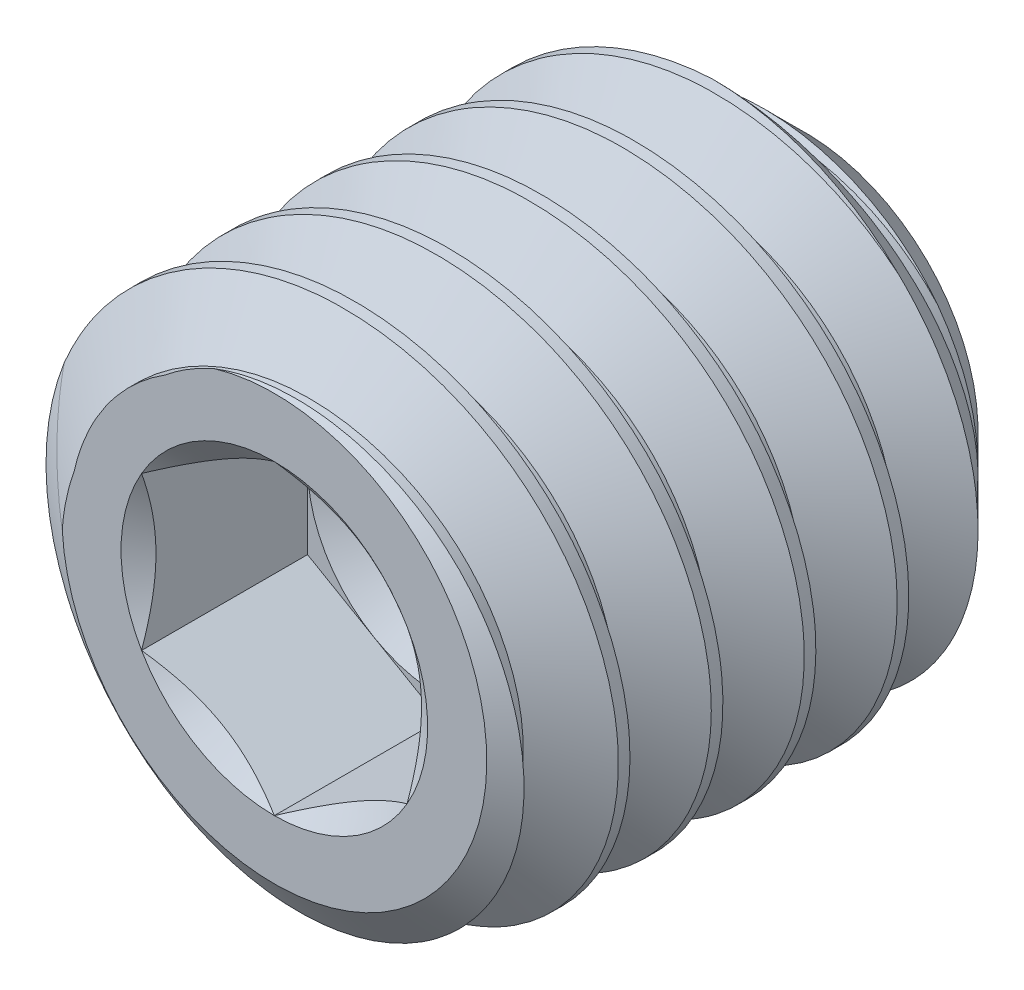
SolidWorks part; units mm, degrees
ref_plane "Front" through (0, 0, 0) normal (0, 0, 1) x (1, 0, 0)
ref_plane "Top" through (0, 0, 0) normal (0, 1, 0) x (1, 0, 0)
ref_plane "Right" through (0, 0, 0) normal (1, 0, 0) x (0, 0, -1)
sketch "Revolve Profile" plane through (0, 0, 0) normal (1, 0, 0) x (0, 0, -1)
  line L0 (-2, 0) -> (-2, 1.6)
  line L1 (-2, 1.6) -> (-1.7199, 2)
  line L2 (-1.7199, 2) -> (1.3, 2)
  line L3 (1.3, 2) -> (2, 1.3)
  line L4 (-0.21, 2) -> (-0.21, -2) construction
  line L5 (2, 0) -> (-2, 0)
  line L6 (-2, 1.6) -> (-2, -1.6) construction
  line L7 (2, 0) -> (2, 1.3)
  point P11 (-0.21, 0)
  dimension "Length" = 4
  dimension "D3" = 35
  dimension "D6" = 45
  dimension "Dia" = 4
  dimension "D1" = 3.2
  dimension "D2" = 0.7
revolve "Body Revolve" add sketch "Revolve Profile" angle 360 about L5
ref_plane "Plane1" through (0, 0, -2) normal (0, 0, 1) x (1, 0, 0)
sketch "Sketch27" plane through (0, 0, -2) normal (0, 0, 1) x (1, 0, 0)
  circle A0 centre (0, 0) radius 2 construction
  circle A1 centre (0, 0) radius 2
curve "Helix/Spiral" pitch 0.7 height 4.7 radius 2 centre (0, 0, -2) axis (0, 0, 1) start towards (0, 1, 0)
sketch "Sketch28" plane through (0, 0, 0) normal (1, 0, 0) x (0, 0, -1)
  line L0 (2, 2) -> (2.6125, 2)
  line L1 (2.6125, 2) -> (2.35, 1.5453)
  line L2 (2.35, 1.5453) -> (2.2625, 1.5453)
  line L3 (2.2625, 1.5453) -> (2, 2)
  line L4 (2.1313, 1.7727) -> (2.4813, 1.7727) construction
  line L6 (-1.7199, 2) -> (1.3, 2) construction
  dimension "D1" = 0.0875
  dimension "D3" = 60
  dimension "D2" = 0.35
sweep "Thread Sweep" cut profiles "Sketch28" path "Helix/Spiral" align with end faces yes
sketch "Hex Sketch" plane through (0, 0, 2) normal (0, 0, 1) x (1, 0, 0)
  line L1 (0, 1.1547) -> (-1, 0.5774)
  line L2 (-1, 0.5774) -> (-1, -0.5774)
  line L3 (-1, -0.5774) -> (0, -1.1547)
  line L4 (0, -1.1547) -> (1, -0.5774)
  line L5 (1, -0.5774) -> (1, 0.5774)
  line L6 (1, 0.5774) -> (0, 1.1547)
  circle A0 centre (0, 0) radius 1 construction
  dimension "Hex" = 2
extrude "Hex Extrude" cut sketch "Hex Sketch" against normal blind 1.25
sketch "Hex Entry Sketch" plane through (0, 0, 2) normal (0, 0, 1) x (1, 0, 0)
  circle A0 centre (0, 0) radius 1.1547
extrude "Hex Entry Extrude" cut sketch "Hex Entry Sketch" against normal through all draft 55
sketch "Hex Bottom Sketch" plane through (0, 0, 0.75) normal (0, 0, 1) x (1, 0, 0)
  circle A0 centre (0, 0) radius 1 construction
  circle A1 centre (0, 0) radius 1
extrude "Hex Bottom Extrude" cut sketch "Hex Bottom Sketch" against normal through all draft 60
equation "\"D1@Sketch28\" = \"D4@Helix/Spiral\" * .125"
equation "\"D2@Sketch28\" = \"D4@Helix/Spiral\" * .5"
equation "\"D3@Helix/Spiral\" = \"Length@Revolve Profile\" + \"D4@Helix/Spiral\""
equation "\"hex Depth@Hex Extrude\" = \"Hex@Hex Sketch\" * .625"
equation "\"D1@Revolve Profile\" = \"Dia@Revolve Profile\" * .8"
equation "\"D2@Revolve Profile\" = \"D4@Helix/Spiral\""
